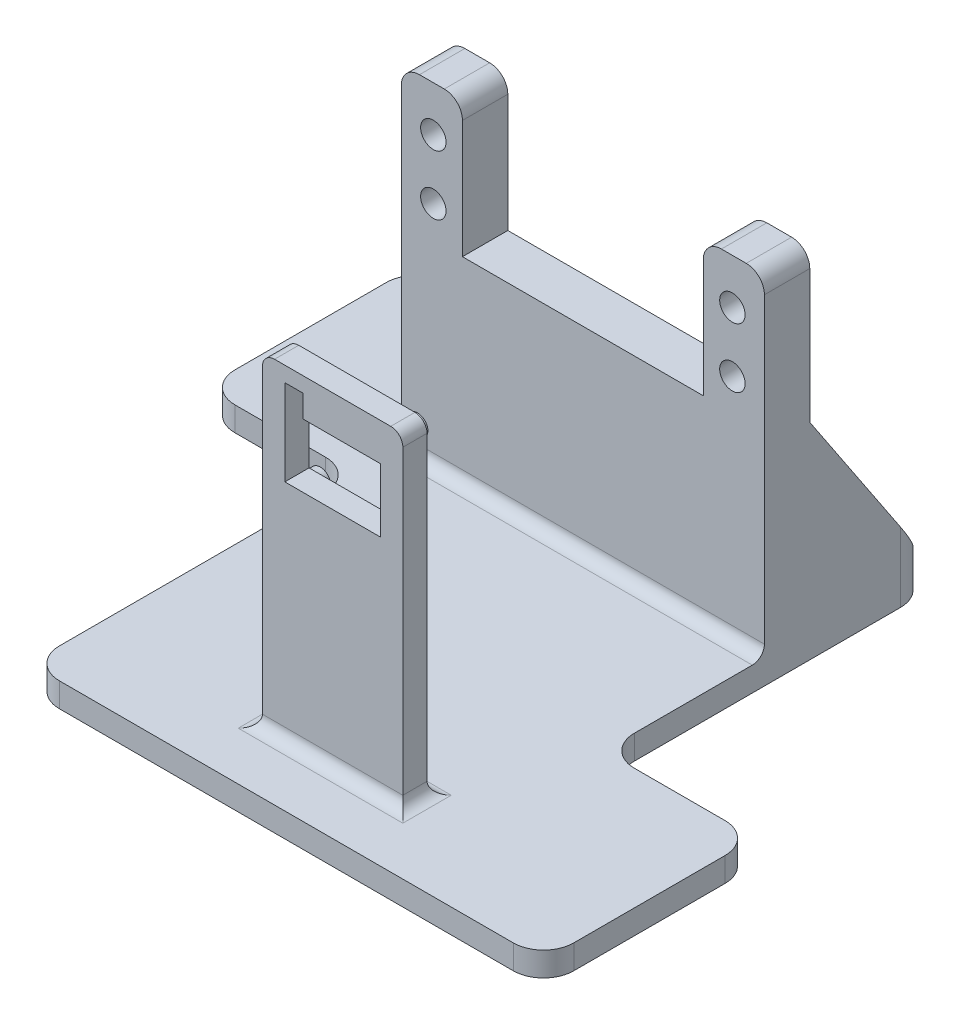
SolidWorks part; units mm, degrees
ref_plane "Front Plane" through (0, 0, 0) normal (0, 0, 1) x (1, 0, 0)
ref_plane "Top Plane" through (0, 0, 0) normal (0, 1, 0) x (1, 0, 0)
ref_plane "Right Plane" through (0, 0, 0) normal (1, 0, 0) x (0, 0, -1)
sketch "Sketch2" plane through (0, 0, 0) normal (0, 0, 1) x (1, 0, 0)
  line L1 (-30, -27.5) -> (30, -27.5)
  line L2 (-30, -27.5) -> (-30, 27.5)
  line L3 (-30, 27.5) -> (30, 27.5)
  line L4 (30, -27.5) -> (30, 27.5)
  line L5 (0, 27.5) -> (0, -27.5) construction
  line L6 (-30, 0) -> (30, 0) construction
  point P0 (0, 0)
  dimension "D1" = 60
  dimension "D2" = 55
extrude "Boss-Extrude1" add sketch "Sketch2" along normal blind 7.5
sketch "Sketch3" plane through (0, 0, 7.5) normal (0, 0, 1) x (1, 0, 0)
  line L0 (30, 27.5) -> (-30, 27.5) construction
  line L1 (-19.9, 50) -> (19.9, 50)
  line L2 (-19.9, 50) -> (-19.9, 5)
  line L3 (-19.9, 5) -> (19.9, 5)
  line L4 (19.9, 50) -> (19.9, 5)
  line L5 (0, 5) -> (0, 50) construction
  line L6 (-19.9, 27.5) -> (19.9, 27.5) construction
  point P0 (0, 27.5)
  dimension "D1" = 39.8
  dimension "D2" = 22.5
extrude "Cut-Extrude1" cut sketch "Sketch3" against normal through all
sketch "Sketch4" plane through (0, 0, 7.5) normal (0, 0, 1) x (1, 0, 0)
  line L0 (-19.9, 5) -> (19.9, 5) construction
  line L1 (0, -1000) -> (0, 49000) construction
  circle A0 centre (-24.71, 20.03) radius 2.1
  circle A1 centre (-24.71, 10.18) radius 2.1
  circle A2 centre (24.71, 20.03) radius 2.1
  circle A3 centre (24.71, 10.18) radius 2.1
  dimension "D1" = 9.85
  dimension "D2" = 5.18
  dimension "D3" = 24.71
extrude "Cut-Extrude2" cut sketch "Sketch4" against normal through all
ref_plane "Plane1" through (0, 0, 56) normal (0, 0, 1) x (1, 0, 0)
sketch "Sketch6" plane through (0, 0, 56) normal (0, 0, 1) x (1, 0, 0)
  line L7 (2.25, 9.6) -> (18.05, 9.6)
  line L8 (2.25, 9.6) -> (2.25, 20.1)
  line L9 (2.25, 20.1) -> (18.05, 20.1)
  line L10 (18.05, 9.6) -> (18.05, 20.1)
  line L11 (10.15, 20.1) -> (10.15, 9.6) construction
  line L12 (2.25, 14.85) -> (18.05, 14.85) construction
  line L14 (-30, 0) -> (30, 0) construction
  line L15 (-1.45, 3.4) -> (21.75, 3.4) construction
  line L16 (-1.45, 3.4) -> (-1.45, 26.3)
  line L17 (-1.45, 26.3) -> (21.75, 26.3)
  line L18 (21.75, 3.4) -> (21.75, 26.3)
  line L19 (10.15, 26.3) -> (10.15, 3.4) construction
  line L20 (-1.45, 14.85) -> (21.75, 14.85) construction
  line L21 (-1.45, 3.4) -> (-1.45, -27.5)
  line L22 (-30, -27.5) -> (30, -27.5) construction
  line L23 (-1.45, -27.5) -> (21.75, -27.5)
  line L24 (21.75, -27.5) -> (21.75, 3.4)
  circle A1 centre (18.194, 22.744) radius 1.7
  circle A2 centre (2.11, 6.956) radius 1.7
  point P0 (10.15, 14.85)
  point P11 (10.15, 14.85)
  dimension "D7" = 3.4
  dimension "D8" = 3.4
  dimension "D9" = 3.556
  dimension "D1" = 15.8
  dimension "D2" = 10.5
  dimension "D3" = 10.15
  dimension "D4" = 14.85
  dimension "D5" = 23.2
  dimension "D6" = 22.9
  dimension "D10" = 3.556
  dimension "D11" = 3.56
  dimension "D12" = 3.556
extrude "Boss-Extrude2" add sketch "Sketch6" along normal blind 3 and the other way blind 1 separate body
sketch "Sketch7" plane through (0, 0, 59) normal (0, 0, 1) x (1, 0, 0)
  line L0 (21.75, 26.3) -> (-1.45, 26.3) construction
  line L1 (2.25, 20.1) -> (5.25, 20.1)
  line L2 (2.25, 20.1) -> (2.25, 23.8)
  line L3 (2.25, 23.8) -> (5.25, 23.8)
  line L4 (5.25, 20.1) -> (5.25, 23.8)
  dimension "D1" = 2.5
  dimension "D2" = 3
extrude "Cut-Extrude3" cut sketch "Sketch7" against normal up to surface (4 mm away) up to face at (10.15, 14.85, 55)
sketch "Sketch8" plane through (0, 0, 59) normal (0, 0, 1) x (1, 0, 0)
  circle A2 centre (18.194, 22.744) radius 1.7 construction
  circle A3 centre (2.11, 6.956) radius 1.7 construction
  circle A4 centre (18.194, 22.744) radius 1.7
  circle A5 centre (2.11, 6.956) radius 1.7
extrude "Boss-Extrude4" add sketch "Sketch8" against normal blind 6
sketch "Sketch10" plane through (0, -27.5, 0) normal (0, -1, 0) x (1, 0, 0)
  line L0 (-30, 0) -> (30, 0) construction
  line L1 (-30, -20) -> (30, -20)
  line L2 (-30, -20) -> (-30, 69)
  line L3 (-30, 69) -> (30, 69)
  line L4 (30, -20) -> (30, 69)
  line L5 (-1.45, 59) -> (21.75, 59) construction
  dimension "D1" = 20
  dimension "D2" = 10
extrude "Boss-Extrude5" add sketch "Sketch10" along normal blind 4
sketch "Sketch11" plane through (30, 0, 0) normal (1, 0, 0) x (0, 0, -1)
  line L0 (0, 2.5) -> (20, -27.5)
  line L1 (0, -27.5) -> (0, 27.5) construction
  line L2 (20, -27.5) -> (0, -27.5)
  line L3 (0, -27.5) -> (0, 2.5)
  dimension "D1" = 30
extrude "Boss-Extrude6" add sketch "Sketch11" against normal blind 4
pattern_linear "LPattern1" count 2 spacing 56 along (-1, 0, 0) of "Boss-Extrude6"
fillet "Fillet1" radius 3 4 edges at (-30, 27.5, 3.75) (-19.9, 27.5, 3.75) (30, 27.5, 3.75) (19.9, 27.5, 3.75)
fillet "Fillet3" radius 2 2 edges at (-1.45, 26.3, 57) (21.75, 26.3, 57)
fillet "Fillet4" radius 2 1 edges at (-1.45, -27.5, 57) type face fillet first side face at (10.15, -27.5, 57) second side face at (-1.45, -1.6, 57)
fillet "Fillet5" radius 2 1 edges at (21.75, -27.5, 57) type face fillet first side face at (9.15, -27.5, 57) second side face at (21.75, -1.6, 57)
fillet "Fillet6" radius 2 1 edges at (0, -27.5, 7.5) type face fillet first side face at (-22.61, 10.18, 7.5) second side face at (10.15, -27.5, 57)
fillet "Fillet7" radius 2 1 edges at (10.15, -27.5, 55) type face fillet first side face at (8.5167, 17.8333, 55) second side face at (10.15, -27.5, 57)
fillet "Fillet8" radius 2 1 edges at (10.15, -27.5, 59) type face fillet first side face at (10.15, -0.6, 59) second side face at (10.15, -27.5, 56)
fillet "Fillet9" radius 2 1 edges at (26, -12.5, 0)
fillet "Fillet10" radius 2 1 edges at (-26, -12.5, 0)
sketch "Sketch12" plane through (0, -31.5, 0) normal (0, -1, 0) x (1, 0, 0)
  line L1 (-30, -20) -> (-55, -20)
  line L2 (-30, -20) -> (-30, 15)
  line L3 (-30, 15) -> (-55, 15)
  line L4 (-55, -20) -> (-55, 15)
  line L5 (30, 69) -> (55, 69)
  line L6 (30, 69) -> (30, 34)
  line L7 (30, 34) -> (55, 34)
  line L8 (55, 69) -> (55, 34)
  dimension "D1" = 35
  dimension "D2" = 25
  dimension "D3" = 35
  dimension "D4" = 25
extrude "Boss-Extrude7" add sketch "Sketch12" against normal up to surface (4 mm away) up to face at (10.15, -27.5, 57)
fillet "Fillet11" radius 5 8 edges at (30, -29.5, -20) (30, -29.5, 34) (55, -29.5, 34) (55, -29.5, 69) (-30, -29.5, 69) (-30, -29.5, 15) (-55, -29.5, 15) (-55, -29.5, -20)
